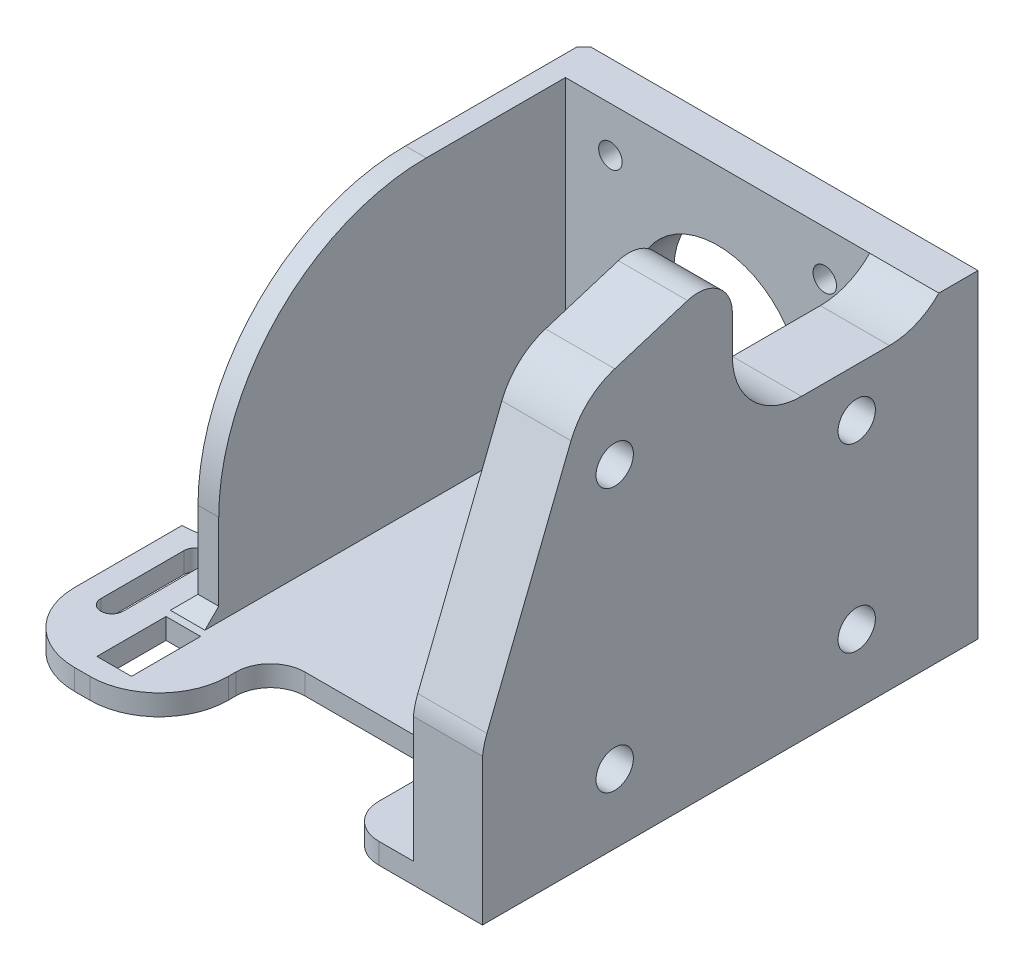
SolidWorks part; units mm, degrees
ref_plane "Спереди" through (0, 0, 0) normal (0, 0, 1) x (1, 0, 0)
ref_plane "Сверху" through (0, 0, 0) normal (0, 1, 0) x (1, 0, 0)
ref_plane "Справа" through (0, 0, 0) normal (1, 0, 0) x (0, 0, -1)
sketch "Эскиз1" plane through (0, 0, 0) normal (0, 0, 1) x (1, 0, 0)
  line L1 (-22, 22) -> (22, 22)
  line L2 (-22, 22) -> (-22, -22)
  line L3 (-22, -22) -> (22, -22)
  line L4 (22, 22) -> (22, -22)
  line L5 (-22, 22) -> (22, -22) construction
  line L6 (-22, -22) -> (22, 22) construction
  point P0 (0, 0)
  dimension "D1" = 44
  dimension "D2" = 44
extrude "Бобышка-Вытянуть2" add sketch "Эскиз1" along normal blind 5
sketch "Эскиз2" plane through (0, 0, 5) normal (0, 0, 1) x (1, 0, 0)
  line L0 (0, 0) -> (-15.5, 0)
  line L1 (-15.5, 0) -> (-15.5, 15.5)
  circle A0 centre (0, 0) radius 10
  circle A1 centre (-15.5, 15.5) radius 1.5
  circle A2 centre (15.5, 15.5) radius 1.5
  circle A3 centre (15.5, -15.5) radius 1.5
  circle A4 centre (-15.5, -15.5) radius 1.5
  dimension "D1" = 20
  dimension "D4" = 3
  dimension "D2" = 15.5
  dimension "D3" = 15.5
  dimension "D5" = 2
  dimension "D6" = 2
extrude "Вырез-Вытянуть1" cut sketch "Эскиз2" against normal through all contours A0 | A3 | A4 | A1 | A2 region at (0, 9.7172, 5) region at (15.5, -15.5, 5) region at (-15.5, -15.5, 5)
sketch "Эскиз3" plane through (0, 0, 5) normal (0, 0, 1) x (1, 0, 0)
  circle A0 centre (0, 0) radius 12
  dimension "D1" = 24
extrude "Вырез-Вытянуть3" cut sketch "Эскиз3" against normal through all contours A0
sketch "Эскиз5" plane through (0, -22, 0) normal (0, -1, 0) x (1, 0, 0)
  line L0 (-22, 5) -> (-22, 52.1428)
  line L1 (-22, 52.1428) -> (22, 52.1428)
  line L2 (22, 52.1428) -> (22, 5)
  line L3 (-22, 5) -> (-22, 0)
  line L4 (-22, 0) -> (22, 0)
  line L5 (22, 0) -> (22, 5)
extrude "Бобышка-Вытянуть4" add sketch "Эскиз5" along normal blind 3 contours L0 L1 L2 L5 L4 L3
sketch "Эскиз6" plane through (0, 0, 52.1428) normal (0, 0, 1) x (1, 0, 0)
  line L0 (22, -22) -> (22, -21.15)
  line L1 (22, -22) -> (22, 22) construction
  line L2 (22, -21.15) -> (-22, -21.15)
  line L3 (-22, 22) -> (-22, -22) construction
  line L4 (-22, -21.15) -> (-22, -22)
  line L5 (-22, -22) -> (22, -22)
  dimension "D1" = 0.85
extrude "Бобышка-Вытянуть5" add sketch "Эскиз6" against normal up to next
sketch "Эскиз7" plane through (0, 0, 52.1428) normal (0, 0, 1) x (1, 0, 0)
  line L0 (22, -25) -> (22, -24.15)
  line L1 (22, -25) -> (22, -21.15) construction
  line L2 (22, -24.15) -> (-22, -24.15)
  line L3 (-22, -25) -> (-22, -21.15) construction
  line L4 (-22, -24.15) -> (-22, -25)
  line L5 (-22, -25) -> (22, -25)
  dimension "D1" = 0.85
extrude "Вырез-Вытянуть4" cut sketch "Эскиз7" against normal through all
sketch "Эскиз8" plane through (-22, 0, 0) normal (-1, 0, 0) x (0, 0, 1)
  line L1 (0, 22) -> (52.1428, 22)
  line L2 (0, 22) -> (0, -24.15)
  line L3 (0, -24.15) -> (52.1428, -24.15)
  line L4 (52.1428, 22) -> (52.1428, -24.15)
extrude "Бобышка-Вытянуть6" add sketch "Эскиз8" along normal blind 3
sketch "Эскиз10" plane through (0, 0, 52.1428) normal (0, 0, 1) x (1, 0, 0)
  line L1 (-25, 22) -> (-22, 22)
  line L2 (-25, 22) -> (-25, -21.15)
  line L3 (-25, -21.15) -> (-22, -21.15)
  line L4 (-22, 22) -> (-22, -21.15)
  line L5 (-25, -21.15) -> (22, -21.15)
  line L6 (-25, -21.15) -> (-25, -24.15)
  line L7 (-25, -24.15) -> (22, -24.15)
  line L8 (22, -21.15) -> (22, -24.15)
  line M4 (-22, -21.15) -> (-22, 22)
  line M5 (-22, 22) -> (-25, 22)
  line M6 (-25, 22) -> (-25, -24.15)
extrude "Бобышка-Вытянуть7" add sketch "Эскиз10" along normal blind 3 contours L3 M6 M4 M5 | L5 L8 L7 L6 region at (-23.5, 0.425, 52.1428)
sketch "Эскиз11" plane through (22, 0, 0) normal (1, 0, 0) x (0, 0, -1)
  line L0 (0, 22) -> (-1, 22)
  line L1 (-5, 22) -> (0, 22) construction
  line L2 (-1, 22) -> (-1, -24.15)
  line L3 (0, -24.15) -> (-55.1428, -24.15) construction
  line L4 (-1, -24.15) -> (0, -24.15)
  line L5 (0, -24.15) -> (0, 22)
  dimension "D1" = 1
extrude "Вырез-Вытянуть5" cut sketch "Эскиз11" against normal through all
sketch "Эскиз12" plane through (0, 0, 1) normal (0, 0, -1) x (-1, 0, 0)
  circle A0 centre (-15.5, 15.5) radius 1.55
  circle A1 centre (15.5, 15.5) radius 1.55
  circle A2 centre (15.5, -15.5) radius 1.55
  circle A3 centre (-15.5, -15.5) radius 1.55
  point P3 (15.5, 15.5)
  dimension "D1" = 3.1
  dimension "D2" = 2
  dimension "D3" = 2
extrude "Вырез-Вытянуть6" cut sketch "Эскиз12" against normal through all
sketch "Эскиз14" plane through (22, 0, 0) normal (1, 0, 0) x (0, 0, -1)
  line L1 (-1, 22) -> (-55.1428, 22)
  line L2 (-1, 22) -> (-1, -24.15)
  line L3 (-1, -24.15) -> (-55.1428, -24.15)
  line L4 (-55.1428, 22) -> (-55.1428, -24.15)
extrude "Бобышка-Вытянуть8" add sketch "Эскиз14" along normal blind 5
sketch "Эскиз15" plane through (27, 0, 0) normal (1, 0, 0) x (0, 0, -1)
  line L0 (-1, 22) -> (-1, 33.4299)
  line L1 (-1, 33.4299) -> (-71, 33.4299)
  line L2 (-71, 33.4299) -> (-71, -24.15)
  line L3 (-71, -24.15) -> (-55.1428, -24.15)
  line L4 (-55.1428, -24.15) -> (-55.1428, 22)
  line L5 (-55.1428, 22) -> (-1, 22)
  dimension "D1" = 70
extrude "Бобышка-Вытянуть9" add sketch "Эскиз15" against normal blind 5
sketch "Эскиз17" plane through (22, 0, 0) normal (-1, 0, 0) x (0, 0, 1)
  line L0 (1, 33.4299) -> (71, 33.4299)
  line L3 (71, 33.4299) -> (71, 46.5506)
  line L5 (1, 33.4299) -> (1, 46.5506)
  line L6 (1, 46.5506) -> (71, 46.5506)
extrude "Бобышка-Вытянуть10" add sketch "Эскиз17" against normal blind 5 contours L6 L3 L0 L5
sketch "Эскиз18" plane through (22, 0, 0) normal (-1, 0, 0) x (0, 0, 1)
  line L0 (76.4365, -49.7979) -> (71, -3.0099)
  line L1 (70.3593, -0.4693) -> (58.2014, 30.1084)
  line L2 (18.3177, 46.4037) -> (51.8796, 35.9623)
  line L3 (71, 46.5506) -> (71, -24.15) construction
  line L5 (71, -3.0099) -> (71, 46.5506)
  line L6 (17.8456, 46.5506) -> (71, 46.5506)
  line L7 (18.3177, 46.4037) -> (17.6683, 46.6057)
  line L8 (1, 46.5506) -> (71, 46.5506) construction
  arc A0 (58.2014, 30.1084) -> (51.8796, 35.9623) centre (48.909, 26.4137) ccw
  arc A1 (70.3593, -0.4693) -> (71, -3.0099) centre (61.0668, -4.164) cw
  line M5 (71, -24.15) -> (71, 46.5506)
  line M6 (71, 46.5506) -> (1, 46.5506)
extrude "Вырез-Вытянуть8" cut sketch "Эскиз18" against normal through all contours L1 A1 L7 L2 A0 M5 M6 region at (22, 34.0135, 57.7413)
sketch "Эскиз21" plane through (27, 0, 0) normal (1, 0, 0) x (0, 0, -1)
  line L0 (-71, -3.0099) -> (-71, -24.15)
  line L1 (-71, -24.15) -> (-1, -24.15)
  line L2 (-1, -24.15) -> (-1, 46.5506)
  line L3 (-1, 46.5506) -> (-17.8456, 46.5506)
  line L10 (5.4348, 53.7933) -> (-51.8796, 35.9623)
  line L11 (-70.3593, -0.4693) -> (-58.2014, 30.1084)
  arc A2 (-70.3593, -0.4693) -> (-71, -3.0099) centre (-61.0668, -4.164) ccw
  arc A3 (-58.2014, 30.1084) -> (-51.8796, 35.9623) centre (-48.909, 26.4137) cw
  line M4 (-17.8456, 46.5506) -> (-51.8796, 35.9623)
  arc M5 (-51.8796, 35.9623) -> (-58.2014, 30.1084) centre (-48.909, 26.4137) ccw
  line M6 (-58.2014, 30.1084) -> (-70.3593, -0.4693)
  arc M7 (-70.3593, -0.4693) -> (-71, -3.0099) centre (-61.0668, -4.164) ccw
  line M8 (-71, -3.0099) -> (-71, -24.15)
  line M9 (-71, -24.15) -> (-1, -24.15)
  line M10 (-1, -24.15) -> (-1, 46.5506)
  line M11 (-1, 46.5506) -> (-17.8456, 46.5506)
extrude "Бобышка-Вытянуть12" add sketch "Эскиз21" along normal blind 5 contours M11 M4 M5 M6 M7 M8 M9 M10 region at (27, 7.5879, 32.5574)
sketch "Эскиз22" plane through (22, 0, 0) normal (-1, 0, 0) x (0, 0, 1)
  line L0 (1, 22) -> (1, 46.5506)
  line L1 (1, 46.5506) -> (17.8456, 46.5506)
  line L2 (17.8456, 46.5506) -> (34.8626, 41.2564)
  line L3 (51.8796, 35.9623) -> (17.8456, 46.5506) construction
  line L4 (34.8626, 41.2564) -> (34.8626, 22)
  line L5 (34.8626, 22) -> (1, 22)
extrude "Вырез-Вытянуть9" cut sketch "Эскиз22" against normal through all
fillet "Скругление2" radius 5 1 edges at (27, 41.2564, 34.8626)
sketch "Эскиз23" plane through (0, -21.15, 0) normal (0, 1, 0) x (1, 0, 0)
  line L1 (22, -55.1428) -> (12, -55.1428)
  line L2 (22, -55.1428) -> (22, -71)
  line L3 (22, -71) -> (12, -71)
  line L4 (12, -55.1428) -> (12, -71)
  dimension "D1" = 10
extrude "Бобышка-Вытянуть13" add sketch "Эскиз23" against normal blind 3
fillet "Скругление3" radius 5 1 edges at (12, -22.65, 55.1428)
fillet "Скругление4" radius 5 1 edges at (12, -22.65, 71)
sketch "Эскиз24" plane through (0, 0, 1) normal (0, 0, -1) x (-1, 0, 0)
sketch "Эскиз25" plane through (0, -24.15, 0) normal (0, -1, 0) x (1, 0, 0)
  line L0 (-25, 45.6914) -> (-39.7734, 45.6914)
  line L1 (-25, 1) -> (-25, 55.1428) construction
  line L2 (-39.7734, 45.6914) -> (-39.7734, 71.2348)
  line L3 (-39.7734, 71.2348) -> (-14.5306, 71.2348)
  line L4 (-14.5306, 71.2348) -> (-14.5306, 45.6914)
  line L5 (-14.5306, 45.6914) -> (-25, 45.6914)
extrude "Бобышка-Вытянуть14" add sketch "Эскиз25" against normal blind 3
fillet "Скругление5" radius 5 1 edges at (-14.5306, -22.65, 55.1428)
sketch "Эскиз26" plane through (0, -21.15, 0) normal (0, 1, 0) x (1, 0, 0)
  line L0 (-39.7734, -45.6914) -> (-36.7734, -45.6914)
  line L1 (-39.7734, -45.6914) -> (-25, -45.6914) construction
  line L2 (-36.7734, -45.6914) -> (-36.7734, -71.2348)
  line L3 (-14.5306, -71.2348) -> (-39.7734, -71.2348) construction
  line L4 (-36.7734, -71.2348) -> (-39.7734, -71.2348)
  line L5 (-39.7734, -71.2348) -> (-39.7734, -45.6914)
  dimension "D1" = 3
extrude "Вырез-Вытянуть10" cut sketch "Эскиз26" against normal through all
fillet "Скругление10" radius 10 2 edges at (-36.7734, -22.65, 71.2348) (-14.5306, -22.65, 71.2348)
fillet "Скругление11" radius 12 1 edges at (-25, -22.65, 45.6914)
chamfer "Фаска1" distance 2 angle 45 2 edges at (-25, -21.15, 44.4182)
sketch "Эскиз27" plane through (0, -21.15, 0) normal (0, 1, 0) x (1, 0, 0)
  line L9 (-33.4867, -48.6914) -> (-33.4867, -60.6914)
  line L10 (-30.2867, -48.6914) -> (-30.2867, -60.6914)
  arc A0 (-30.2867, -48.6914) -> (-33.4867, -48.6914) centre (-31.8867, -48.6914) ccw
  arc A1 (-33.4867, -60.6914) -> (-30.2867, -60.6914) centre (-31.8867, -60.6914) ccw
  dimension "D2" = 3.2
  dimension "D4" = 3.2
  dimension "D3" = 12
extrude "Вырез-Вытянуть11" cut sketch "Эскиз27" against normal through all
fillet "Скругление12" radius 30 1 edges at (-23.5, 22, 55.1428)
sketch "Эскиз28" plane through (0, -21.15, 0) normal (0, 1, 0) x (1, 0, 0)
  line L0 (-24.5306, -71.2348) -> (-24.5306, -58.2348)
  line L1 (-24.5306, -58.2348) -> (-22.5306, -58.2348)
  line L2 (-22.5306, -58.2348) -> (-22.5306, -68.2348)
  line L3 (-22.5306, -68.2348) -> (-26.5306, -68.2348)
  line L4 (-26.5306, -68.2348) -> (-26.5306, -58.2348)
  line L5 (-26.5306, -58.2348) -> (-24.5306, -58.2348)
  dimension "D1" = 13
  dimension "D2" = 10
  dimension "D3" = 4
extrude "Вырез-Вытянуть12" cut sketch "Эскиз28" against normal blind 5 contours L3 L2 L1 L0 | L5 L4 L3 L0 region at (-25.5306, -21.15, 63.2348) region at (-23.5306, -21.15, 63.2348)
chamfer "Фаска2" distance 1 angle 45 1 edges at (-25, -1.075, 1)
sketch "Эскиз29" plane through (32, 0, 0) normal (1, 0, 0) x (0, 0, -1)
  line L0 (-51.8796, 35.9623) -> (-51.8796, 23.9623)
  line L1 (-51.8796, 23.9623) -> (-46.8796, 23.9623)
  line L2 (-51.8796, 23.9623) -> (-51.8796, -24.15)
  line L3 (-71, -24.15) -> (-1, -24.15) construction
  line L4 (-51.8796, -24.15) -> (-51.8796, -14.15)
  line L5 (-51.8796, -14.15) -> (-16.8796, -14.15)
  line L6 (-16.8796, -14.15) -> (-16.8796, 12)
  line L7 (-16.8796, 12) -> (-16.8796, 22)
  line L8 (-1, 22) -> (-34.8626, 22) construction
  circle A0 centre (-46.8796, 23.9623) radius 2.55
  circle A1 centre (-51.8796, -14.15) radius 2.55
  circle A2 centre (-16.8796, -14.15) radius 2.55
  circle A3 centre (-16.8796, 12) radius 2.55
  dimension "D3" = 5.1
  dimension "D1" = 12
  dimension "D2" = 5
  dimension "D4" = 10
  dimension "D5" = 35
  dimension "D6" = 10
extrude "Вырез-Вытянуть14" cut sketch "Эскиз29" against normal blind 12 contours A0 | L2 A1 L5 | L5 A1 L2 | L2 A1 | L5 A2 L6 | L6 A2 L5 | L6 A3 L7 | L7 A3 L6 region at (32, 26.4401, 46.8796) region at (32, 12, 17.9619) region at (32, 12, 15.7974) region at (32, -13.0677, 17.9619) region at (32, -14.5108, 16.5189) region at (32, -13.0677, 50.7974) region at (32, -14.15, 52.9619) region at (32, -15.2323, 50.7974)
sketch "Эскиз30" plane through (22, 0, 0) normal (-1, 0, 0) x (0, 0, 1)
  circle A0 centre (46.8796, 23.9623) radius 4.5
  circle A1 centre (16.8796, 12) radius 4.5
  circle A2 centre (16.8796, -14.15) radius 4.5
  circle A3 centre (51.8796, -14.15) radius 4.5
  dimension "D1" = 9
extrude "Вырез-Вытянуть15" cut sketch "Эскиз30" against normal blind 4
fillet "Скругление13" radius 1 4 edges at (22, 19.4623, 46.8796) (22, -18.65, 51.8796) (22, -18.65, 16.8796) (22, 7.5, 16.8796)
sketch "Эскиз31" plane through (32, 0, 0) normal (1, 0, 0) x (0, 0, -1)
  line L0 (-16.8796, 12) -> (-56.3151, 12)
  line L1 (-46.8796, 23.9623) -> (-46.8796, 12)
  line L2 (-51.8796, 12) -> (-51.8796, 23.9623)
  circle A0 centre (-51.8796, 23.9623) radius 2.5
  circle M6 centre (-46.8796, 23.9623) radius 2.55
  dimension "D2" = 5
  dimension "D1" = 35
sketch "Эскиз33" plane through (22, 0, 0) normal (-1, 0, 0) x (0, 0, 1)
  circle A0 centre (46.8796, 23.9623) radius 7.0465
extrude "Бобышка-Вытянуть15" add sketch "Эскиз33" against normal blind 10
extrude "Вырез-Вытянуть16" cut sketch "Эскиз31" against normal through all contours A0 M6 region at (32, 23.9623, 51.8826)
sketch "Эскиз35" plane through (22, 0, 0) normal (-1, 0, 0) x (0, 0, 1)
  circle A0 centre (51.8796, 23.9623) radius 4.5
  dimension "D1" = 9
extrude "Вырез-Вытянуть17" cut sketch "Эскиз35" against normal blind 4
fillet "Скругление15" radius 1 1 edges at (22, 19.4623, 51.8796)
sketch "Эскиз36" plane through (0, 0, 1) normal (0, 0, -1) x (-1, 0, 0)
  circle A0 centre (-15.5, 15.5) radius 1.7
  circle A1 centre (15.5, 15.5) radius 1.7
  circle A2 centre (15.5, -15.5) radius 1.7
  circle A3 centre (-15.5, -15.5) radius 1.7
  dimension "D1" = 3.4
extrude "Вырез-Вытянуть18" cut sketch "Эскиз36" against normal blind 10
sketch "Эскиз37" plane through (0, 0, 1) normal (0, 0, -1) x (-1, 0, 0)
  line L1 (-32, -24.15) -> (25, -24.15)
  line L2 (-32, -24.15) -> (-32, 22)
  line L3 (-32, 22) -> (25, 22)
  line L4 (25, -24.15) -> (25, 22)
  circle A0 centre (-15.5, -15.5) radius 1.7
  circle A1 centre (15.5, -15.5) radius 1.7
  circle A2 centre (15.5, 15.5) radius 1.7
  circle A3 centre (-15.5, 15.5) radius 1.7
  dimension "D1" = 3.4
extrude "Бобышка-Вытянуть16" add sketch "Эскиз37" along normal blind 1.66 and the other way blind 2
chamfer "Фаска3" distance 1 angle 45 1 edges at (-25, -1.075, -0.66)
sketch "Эскиз38" plane through (22, 0, 0) normal (-1, 0, 0) x (0, 0, 1)
  line L0 (5, -21.15) -> (5, 22) construction
  line L1 (34.8626, 22) -> (5, 22)
  line L2 (34.8626, 22) -> (34.8626, 19)
  line L3 (34.8626, 19) -> (5, 19)
  line L4 (5, 22) -> (5, 19)
  dimension "D1" = 3
extrude "Вырез-Вытянуть19" cut sketch "Эскиз38" against normal through all
fillet "Скругление16" radius 10 2 edges at (27, 19, 34.8626) (27, 19, 5)
sketch "Эскиз39" plane through (32, 0, 0) normal (1, 0, 0) x (0, 0, -1)
  circle A0 centre (-51.8796, 23.9623) radius 2.7
  circle A1 centre (-16.8796, 12) radius 2.7
  circle A2 centre (-16.8796, -14.15) radius 2.7
  circle A3 centre (-51.8796, -14.15) radius 2.7
  dimension "D1" = 5.4
extrude "Вырез-Вытянуть20" cut sketch "Эскиз39" against normal blind 10
sketch "Эскиз40" plane through (0, 0, 5) normal (0, 0, 1) x (1, 0, 0)
  circle A0 centre (0, 0) radius 12
extrude "Вырез-Вытянуть21" cut sketch "Эскиз40" against normal blind 10
sketch "Эскиз41" plane through (22, 0, 0) normal (-1, 0, 0) x (0, 0, 1)
  circle A0 centre (51.8796, 23.9623) radius 5.5
  circle A1 centre (51.8796, -14.15) radius 5.5
  circle A2 centre (16.8796, 12) radius 5.5
  circle A3 centre (16.8796, -14.15) radius 5.5
extrude "Вырез-Вытянуть22" cut sketch "Эскиз41" against normal up to surface (4 mm away) up to face at (26, 9.3, 16.8796)
fillet "Скругление17" radius 1 4 edges at (22, -19.65, 51.8796) (22, -19.65, 16.8796) (22, 18.4623, 51.8796) (22, 6.5, 16.8796)
sketch "Эскиз42" plane through (0, -21.15, 0) normal (0, 1, 0) x (1, 0, 0)
  line L1 (-26.5306, -58.2348) -> (-21.5306, -58.2348)
  line L2 (-26.5306, -58.2348) -> (-26.5306, -68.2348)
  line L3 (-26.5306, -68.2348) -> (-21.5306, -68.2348)
  line L4 (-21.5306, -58.2348) -> (-21.5306, -68.2348)
  dimension "D1" = 5
extrude "Вырез-Вытянуть23" cut sketch "Эскиз42" against normal blind 10
